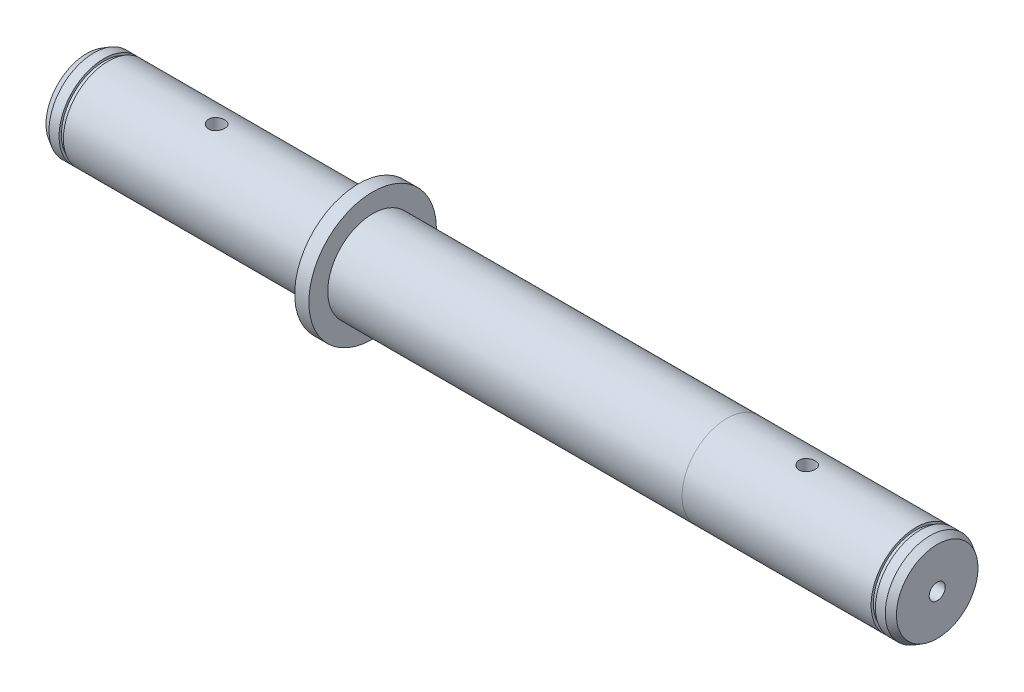
SolidWorks part; units mm, degrees
material "1.7225 (42CrMo4)"
ref_plane "E_Oben" through (0, 0, 0) normal (0, 0, 1) x (1, 0, 0)
ref_plane "E_Vorne" through (0, 0, 0) normal (0, 1, 0) x (1, 0, 0)
ref_plane "E_Rechts" through (0, 0, 0) normal (1, 0, 0) x (0, 0, -1)
ref_axis "A_Drehachse" through (-88.99, 0, 0) along (1, 0, 0)
sketch "Skizze1" plane through (0, 0, 0) normal (0, 0, 1) x (1, 0, 0)
  line L1 (0, -55) -> (0, 55) construction
  line L3 (180, 19) -> (180, 0)
  line L4 (180, 0) -> (-180, 0)
  line L7 (-180, 19) -> (-180, 0)
  line L10 (-65, 19) -> (-65, 27)
  line L11 (-65, 27) -> (-59, 27)
  line L12 (-59, 27) -> (-59, 19.0001)
  line L13 (-180, 19) -> (-65, 19)
  line L14 (-59, 19.0001) -> (91, 19.0001)
  line L15 (91, 19.0001) -> (91, 19)
  line L16 (91, 19) -> (180, 19)
  point P12 (0, 0)
  point P19 (-62, 27)
  dimension "D1" = 19.0001
  dimension "D2" = 19
  dimension "D3" = 19
  dimension "D4" = 360
  dimension "D5" = 115
  dimension "D6" = 6
  dimension "D7" = 27
  dimension "D8" = 150
revolve "Rotation1" add sketch "Skizze1" angle 360 about L4
hole_wizard "M8 Tapped Hole1" positions "Skizze13" profile "Skizze14" tap size "M8" standard "DIN"
sketch "Skizze13" plane through (180, 0, 0) normal (1, 0, 0) x (0, 0, -1)
  point P0 (0, 0)
  point P3 (0, 0)
sketch "Skizze14" plane through (180, 0, 0) normal (0, 1, 0) x (0, 0, -1)
  line L0 (0, 0) -> (0, 67.0429)
  line L1 (0, 67.0429) -> (3.4, 65)
  line L2 (3.4, 65) -> (3.4, 0)
  line L5 (3.4, 0) -> (0, 0)
  line L10 (0, 67.0429) -> (-3.4, 65) construction
  line L11 (0, -6.35) -> (0, 107.95) construction
  dimension "Bohrerdurchmesser" = 6.8
  dimension "Bohrungstiefe" = 65
  dimension "Spitzenwinkel" = 118
cosmetic thread "Bohrungsgewinde2" parameters "D1"=20, "D2"=8
hole_wizard "M8 Gewindebohrung3" positions "Skizze17" profile "Skizze18" tap size "M8" standard "DIN" end condition through all
sketch "Skizze17" plane through (0, 0, 0) normal (0, 1, 0) x (1, 0, 0)
  line L0 (-55, 0) -> (55, 0) construction
  line L1 (-88.99, 0) -> (88.99, 0) construction
  line L3 (180, -19) -> (180, 19) construction
  point P0 (-125, 0)
  point P4 (125, 0)
  dimension "D3" = 305
  dimension "D4" = 55
sketch "Skizze18" plane through (-125, 0, 0) normal (1, 0, 0) x (0, 0, -1)
  line L0 (0, 0) -> (0, 27)
  line L1 (0, 27) -> (3.4, 27)
  line L2 (3.4, 27) -> (3.4, 0)
  line L5 (3.4, 0) -> (0, 0)
  line L11 (0, -6.35) -> (0, 107.95) construction
  dimension "Bohrerdurchmesser" = 6.8
  dimension "Bohrungstiefe" = 27
mirror "Spiegeln2" about plane through (0, 0, 0) normal (0, 1, 0) of "M8 Gewindebohrung3"
sketch "Skizze19" plane through (0, 0, 0) normal (0, 0, 1) x (1, 0, 0)
  line L8 (180, 19) -> (128.4, 19) construction
  line L9 (171, 19) -> (172.85, 19)
  line L10 (171, 19) -> (171, 18)
  line L11 (171, 18) -> (172.85, 18)
  line L12 (172.85, 19) -> (172.85, 18)
  line L13 (180, -19) -> (180, 19) construction
  dimension "D1" = 7.15
  dimension "D2" = 1
  dimension "D4" = 1.85
revolve "Schnitt-Rotation1" cut sketch "Skizze19" angle 360 about axis through (-88.99, 0, 0) along (1, 0, 0)
sketch "Skizze20" plane through (0, 0, 0) normal (0, 0, 1) x (1, 0, 0)
  line L9 (-128.3999, 19) -> (-180, 19) construction
  line L10 (-180, 19) -> (-180, -19) construction
  line L11 (-172.75, 19) -> (-170.9, 19)
  line L12 (-172.75, 19) -> (-172.75, 18)
  line L13 (-172.75, 18) -> (-170.9, 18)
  line L14 (-170.9, 19) -> (-170.9, 18)
  dimension "D1" = 7.25
  dimension "D4" = 1
  dimension "D5" = 1.85
revolve "Schnitt-Rotation2" cut sketch "Skizze20" angle 360 about axis through (-88.99, 0, 0) along (1, 0, 0)
sketch "Sketch3" plane through (-180, 0, 0) normal (-1, 0, 0) x (0, 0, 1)
  point P0 (0, 0)
hole_wizard "M8 Tapped Hole2" positions "Sketch3" profile "Sketch2" tap size "M8" standard "DIN"
sketch "Sketch2" plane through (-180, 0, 0) normal (0, 1, 0) x (0, 0, 1)
  line L0 (0, 0) -> (0, 67.0429)
  line L1 (0, 67.0429) -> (3.4, 65)
  line L2 (3.4, 65) -> (3.4, 0)
  line L5 (3.4, 0) -> (0, 0)
  line L10 (0, 67.0429) -> (-3.4, 65) construction
  line L11 (0, -6.35) -> (0, 107.95) construction
  dimension "Tap Drill Dia." = 6.8
  dimension "Tap Drill Depth" = 65
  dimension "Drill Angle" = 118
cosmetic thread "Hole Thread1" parameters "D1"=20, "D2"=8
chamfer "Fase1" distance 3 angle 30 2 edges at (180, 0, -19) (-180, 0, -19) first distance on face at (180, 0, -19) first distance on face at (-180, 0, -19)
